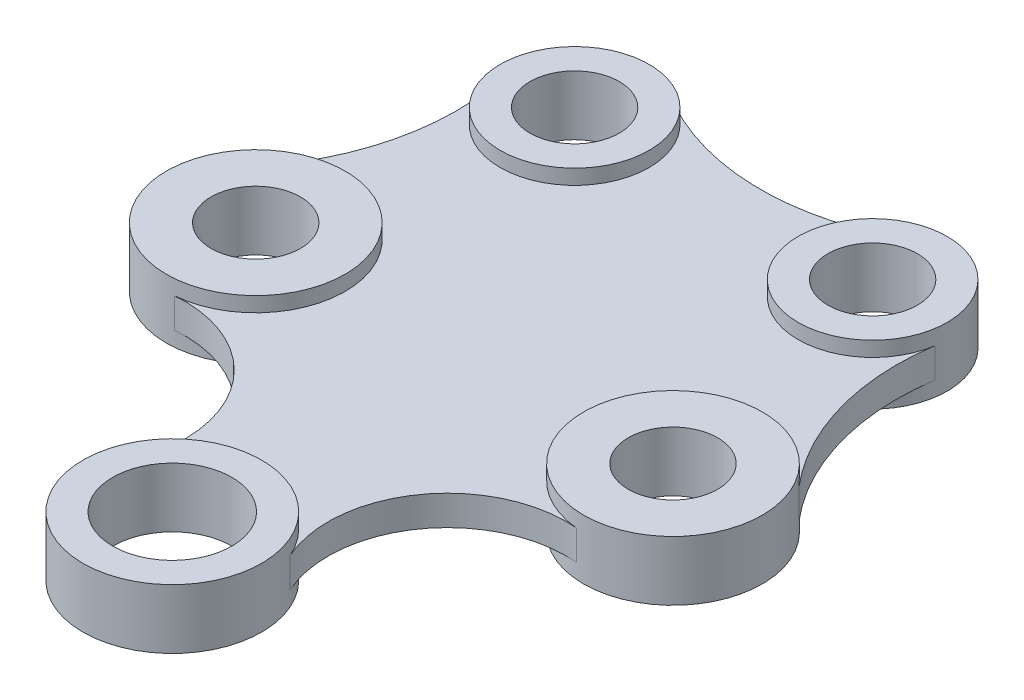
SolidWorks part; units mm, degrees
ref_plane "Front Plane" through (0, 0, 0) normal (0, 0, 1) x (1, 0, 0)
ref_plane "Top Plane" through (0, 0, 0) normal (0, 1, 0) x (1, 0, 0)
ref_plane "Right Plane" through (0, 0, 0) normal (1, 0, 0) x (0, 0, -1)
sketch "Sketch1" plane through (0, 0, 0) normal (0, 1, 0) x (1, 0, 0)
  line L0 (0, 0) -> (0, 78.5736) construction
  line L1 (0, 0) -> (117.6209, 0) construction
  arc A0 (-38.0952, 108.9836) -> (-74.7169, 83.2486) centre (-50, 87) ccw
  circle A1 centre (-50, 87) radius 15
  arc A4 (-92.8576, 19.4302) -> (-67.4477, -29.8912) centre (-70, 0) ccw
  circle A7 centre (-70, 0) radius 15
  arc A8 (-27.4477, -85.8912) -> (27.4477, -85.8912) centre (0, -98) ccw
  circle A9 centre (0, -98) radius 20
  circle A10 centre (70, 0) radius 15
  arc A11 (92.8576, 19.4302) -> (67.4477, -29.8912) centre (70, 0) cw
  circle A12 centre (50, 87) radius 15
  arc A13 (38.0952, 108.9836) -> (74.7169, 83.2486) centre (50, 87) cw
  arc A14 (-92.8576, 19.4302) -> (-74.7169, 83.2486) centre (-153.8111, 71.2439) ccw
  arc A15 (-38.0952, 108.9836) -> (38.0952, 108.9836) centre (0, 179.3309) ccw
  arc A16 (92.8576, 19.4302) -> (74.7169, 83.2486) centre (153.8111, 71.2439) cw
  arc A17 (-27.4477, -85.8912) -> (-67.4477, -29.8912) centre (-64.0447, -69.7462) ccw
  arc A18 (27.4477, -85.8912) -> (67.4477, -29.8912) centre (64.0447, -69.7462) cw
  dimension "D1" = 50
  dimension "D2" = 30
  dimension "D7" = 80
  dimension "D8" = 80
  dimension "D9" = 80
  dimension "D10" = 60
  dimension "D11" = 40
  dimension "D12" = 60
  dimension "D13" = 30
  dimension "D3" = 87
  dimension "D4" = 98
  dimension "D5" = 50
  dimension "D6" = 20
extrude "Boss-Extrude2" add sketch "Sketch1" along normal blind 10
sketch "Sketch3" plane through (0, 10, 0) normal (0, 1, 0) x (1, 0, 0)
  circle A0 centre (-50, 87) radius 25
  circle A1 centre (50, 87) radius 25
  circle A2 centre (70, 0) radius 30
  circle A3 centre (0, -98) radius 30
  circle A4 centre (-70, 0) radius 30
  arc A5 (-38.0952, 108.9836) -> (-74.7169, 83.2486) centre (-50, 87) ccw construction
  arc A6 (-92.8576, 19.4302) -> (-67.4477, -29.8912) centre (-70, 0) ccw construction
  arc A7 (67.4477, -29.8912) -> (92.8576, 19.4302) centre (70, 0) ccw construction
  arc A8 (74.7169, 83.2486) -> (38.0952, 108.9836) centre (50, 87) ccw construction
  arc A9 (-27.4477, -85.8912) -> (27.4477, -85.8912) centre (0, -98) ccw construction
extrude "Boss-Extrude3" add sketch "Sketch3" along normal blind 5 and the other way blind 15
extrude "Cut-Extrude1" cut sketch "Sketch1<4>" against normal mid plane 50 contours A12 | A1 | A7 | A10 | A9
sketch "Sketch1<4>" plane through (0, 0, 0) normal (0, 1, 0) x (1, 0, 0) same geometry as "Sketch1"
